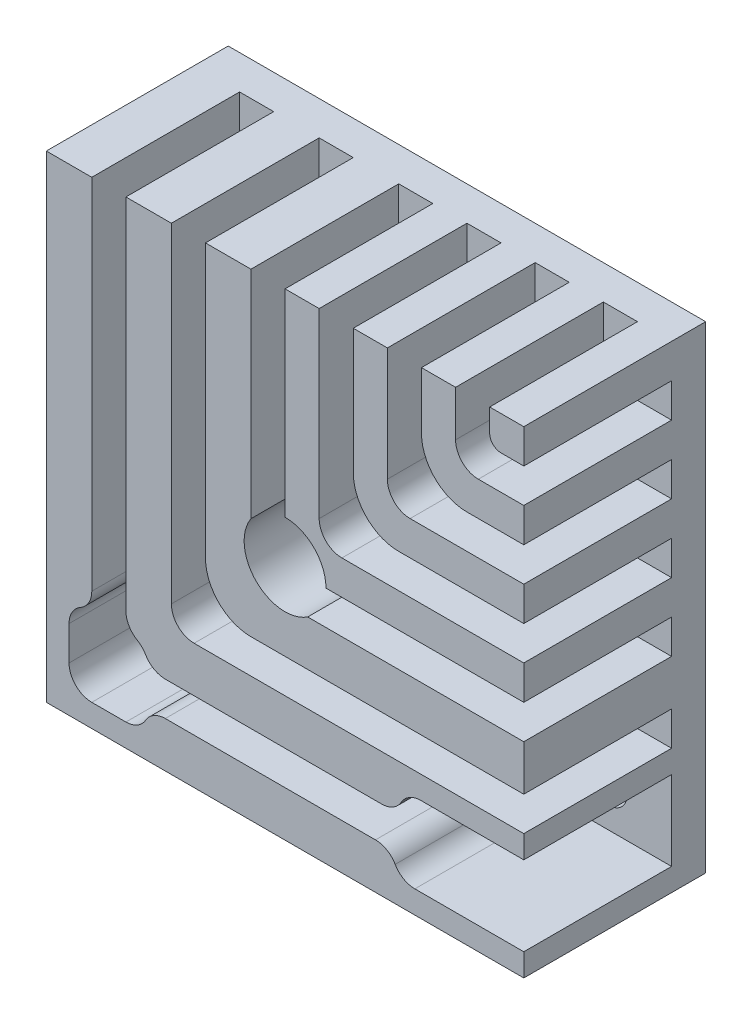
SolidWorks part; units mm, degrees
ref_plane "Front Plane" through (0, 0, 0) normal (0, 0, 1) x (1, 0, 0)
ref_plane "Top Plane" through (0, 0, 0) normal (0, 1, 0) x (1, 0, 0)
ref_plane "Right Plane" through (0, 0, 0) normal (1, 0, 0) x (0, 0, -1)
sketch "Sketch1" plane through (0, 0, 0) normal (0, 0, 1) x (1, 0, 0)
  line L1 (0, 0) -> (42, 0)
  line L2 (0, 0) -> (0, 42)
  line L3 (0, 42) -> (42, 42)
  line L4 (42, 0) -> (42, 42)
  dimension "D1" = 42
  dimension "D2" = 42
extrude "Boss-Extrude1" add sketch "Sketch1" along normal blind 16
sketch "Sketch2" plane through (0, 0, 16) normal (0, 0, 1) x (1, 0, 0)
  line L0 (42, 42) -> (0, 42) construction
  line L1 (42, 0) -> (42, 42) construction
  line L2 (0, 42) -> (0, 0) construction
  line L3 (0, 0) -> (42, 0) construction
  line L4 (38.7689, 42) -> (36.0649, 42)
  line L5 (42, 36.0649) -> (42, 38.7689)
  line L6 (42, 33.5265) -> (42, 30.3811)
  line L7 (33.5265, 42) -> (30.3811, 42)
  line L8 (27.5668, 42) -> (24.7524, 42)
  line L9 (42, 27.5668) -> (42, 24.7524)
  line L10 (42, 21.607) -> (42, 18.572)
  line L11 (42, 15.0403) -> (42, 11.7293)
  line L12 (42, 9.3012) -> (42, 5.6592)
  line L13 (42, 1.079) -> (42, 0)
  line L14 (42, 0) -> (34.9613, 0)
  line L15 (21.607, 42) -> (18.572, 42)
  line L16 (15.0403, 42) -> (11.7293, 42)
  line L17 (9.3012, 42) -> (5.6592, 42)
  line L18 (1.079, 42) -> (0, 42)
  line L19 (0, 42) -> (0, 34.9613)
  line L20 (0, 27.58) -> (0, 15.9232)
  line L21 (0, 9.7979) -> (0, 4.5769)
  line L22 (4.5769, 0) -> (9.7979, 0)
  line L23 (27.58, 0) -> (15.9232, 0)
  arc A0 (38.7689, 42) -> (42, 38.7689) centre (42, 42) ccw
  arc A1 (36.0649, 42) -> (42, 36.0649) centre (42, 42) ccw
  arc A2 (33.5265, 42) -> (42, 33.5265) centre (42, 42) ccw
  arc A3 (30.3811, 42) -> (42, 30.3811) centre (42, 42) ccw
  arc A4 (27.5668, 42) -> (42, 27.5668) centre (42, 42) ccw
  arc A5 (24.7524, 42) -> (42, 24.7524) centre (42, 42) ccw
  arc A6 (21.607, 42) -> (42, 21.607) centre (42, 42) ccw
  arc A7 (18.572, 42) -> (42, 18.572) centre (42, 42) ccw
  arc A8 (15.0403, 42) -> (42, 15.0403) centre (42, 42) ccw
  arc A9 (11.7293, 42) -> (42, 11.7293) centre (42, 42) ccw
  arc A10 (9.3012, 42) -> (42, 9.3012) centre (42, 42) ccw
  arc A11 (5.6592, 42) -> (42, 5.6592) centre (42, 42) ccw
  arc A12 (1.079, 42) -> (42, 1.079) centre (42, 42) ccw
  arc A13 (0, 34.9613) -> (34.9613, 0) centre (42, 42) ccw
  arc A14 (0, 27.58) -> (27.58, 0) centre (42, 42) ccw
  arc A15 (0, 15.9232) -> (15.9232, 0) centre (42, 42) ccw
  arc A16 (0, 9.7979) -> (9.7979, 0) centre (42, 42) ccw
  arc A17 (0, 4.5769) -> (4.5769, 0) centre (42, 42) ccw
extrude "Cut-Extrude1" [suppressed] cut sketch "Sketch2" against normal blind 13
sketch "Sketch3" plane through (0, 0, 16) normal (0, 0, 1) x (1, 0, 0)
  line L2 (39, 42) -> (39, 39)
  line L3 (42, 42) -> (0, 42) construction
  line L4 (39, 39) -> (42, 39)
  line L5 (42, 0) -> (42, 42) construction
  line L6 (42, 36) -> (36, 36)
  line L7 (36, 36) -> (36, 42)
  line L8 (33, 42) -> (33, 33)
  line L9 (33, 33) -> (42, 33)
  line L10 (30, 42) -> (30, 30)
  line L11 (30, 30) -> (42, 30)
  line L12 (42, 27) -> (27, 27)
  line L13 (27, 27) -> (27, 42)
  line L14 (24, 42) -> (24, 24)
  line L15 (24, 24) -> (42, 24)
  line L16 (42, 21) -> (21, 21)
  line L17 (21, 21) -> (21, 42)
  line L18 (18, 42) -> (18, 18)
  line L19 (18, 18) -> (42, 18)
  line L20 (42, 14) -> (14, 14)
  line L21 (14, 14) -> (14, 42)
  line L22 (11, 42) -> (11, 11)
  line L23 (11, 11) -> (42, 11)
  line L24 (42, 7) -> (7, 7)
  line L25 (7, 7) -> (7, 42)
  line L26 (4, 42) -> (4, 4)
  line L27 (4, 4) -> (42, 4)
  line L28 (42, 39) -> (42, 36)
  line L29 (39, 42) -> (36, 42)
  line L30 (33, 42) -> (30, 42)
  line L31 (27, 42) -> (24, 42)
  line L32 (21, 42) -> (18, 42)
  line L33 (14, 42) -> (11, 42)
  line L34 (7, 42) -> (4, 42)
  line L35 (42, 4) -> (42, 7)
  line L36 (42, 11) -> (42, 14)
  line L37 (42, 18) -> (42, 21)
  line L38 (42, 24) -> (42, 27)
  line L39 (42, 30) -> (42, 33)
  dimension "D1" = 3
  dimension "D2" = 3
  dimension "D3" = 3
  dimension "D4" = 3
  dimension "D5" = 3
  dimension "D6" = 3
  dimension "D7" = 3
  dimension "D8" = 3
  dimension "D9" = 4
  dimension "D10" = 3
  dimension "D11" = 4
  dimension "D12" = 3
  dimension "D13" = 3
  dimension "D14" = 3
  dimension "D15" = 3
  dimension "D16" = 3
  dimension "D17" = 3
  dimension "D18" = 3
  dimension "D19" = 3
  dimension "D20" = 3
  dimension "D21" = 4
  dimension "D22" = 3
  dimension "D23" = 4
  dimension "D24" = 3
extrude "Cut-Extrude2" cut sketch "Sketch3" against normal blind 13
fillet "Fillet2" radius 1 1 edges at (39, 39, 9.5) type face fillet first side face at (39, 40.5, 9.5) second side face at (40.5, 39, 9.5)
fillet "Fillet3" radius 4 1 edges at (33, 33, 9.5) type face fillet first side face at (33, 37.5, 9.5) second side face at (37.5, 33, 9.5)
fillet "Fillet4" radius 4 1 edges at (27, 27, 9.5) type face fillet first side face at (27, 34.5, 9.5) second side face at (34.5, 27, 9.5)
fillet "Fillet6" radius 4 1 edges at (14, 14, 9.5) type face fillet first side face at (14, 28, 9.5) second side face at (28, 14, 9.5)
fillet "Fillet8" radius 2 1 edges at (36, 36, 9.5) type face fillet first side face at (36, 39, 9.5) second side face at (39, 36, 9.5)
fillet "Fillet9" radius 2 1 edges at (30, 30, 9.5) type face fillet first side face at (30, 36, 9.5) second side face at (36, 30, 9.5)
fillet "Fillet11" radius 2 1 edges at (18, 18, 9.5) type face fillet first side face at (18, 30, 9.5) second side face at (30, 18, 9.5)
fillet "Fillet12" radius 2 1 edges at (11, 11, 9.5) type face fillet first side face at (11, 26.5, 9.5) second side face at (26.5, 11, 9.5)
fillet "Fillet13" radius 2 1 edges at (4, 4, 9.5) type face fillet first side face at (4, 23, 9.5) second side face at (23, 4, 9.5)
sketch "Sketch4" plane through (0, 0, 0) normal (0, 0, -1) x (-1, 0, 0)
  line L0 (-42, 5.5) -> (0, 5.5) construction
  line L1 (-42, 0) -> (-42, 42) construction
  line L2 (0, 42) -> (0, 0) construction
  line L3 (-5.5, 0) -> (-5.5, 42) construction
  line L4 (0, 0) -> (-42, 0) construction
  line L5 (-42, 42) -> (0, 42) construction
  line L6 (-36.5, 0) -> (-36.5, 42) construction
  line L7 (-21, 0) -> (-21, 42) construction
  line L8 (-42, 21) -> (0, 21) construction
  circle A0 centre (-36.5, 5.5) radius 1.6
  circle A1 centre (-5.5, 5.5) radius 1.6
  circle A2 centre (-21, 21) radius 3.6
  dimension "D4" = 3.2
  dimension "D5" = 7.2
  dimension "D1" = 5.5
  dimension "D2" = 5.5
  dimension "D3" = 5.5
extrude "Cut-Extrude3" cut sketch "Sketch4" against normal up to next
sketch "Sketch5" plane through (0, 0, 16) normal (0, 0, 1) x (1, 0, 0)
  line L16 (30.9533, 9) -> (42.0467, 2) construction
  line L17 (30.9533, 2) -> (42.0467, 2)
  line L18 (30.9533, 2) -> (30.9533, 9)
  line L19 (30.9533, 9) -> (42.0467, 9)
  line L20 (42.0467, 2) -> (42.0467, 9)
  line L21 (42.0467, 9) -> (30.9533, 2) construction
  line L22 (5.5, 9) -> (5.5, 2) construction
  line L23 (2, 2) -> (9, 2)
  line L24 (2, 2) -> (2, 9)
  line L25 (2, 9) -> (9, 9)
  line L26 (9, 2) -> (9, 9)
  line L27 (2, 5.5) -> (9, 5.5) construction
  arc A10 (37.0568, 4) -> (37.0568, 7) centre (36.5, 5.5) ccw construction
  arc A11 (6.0568, 4) -> (4, 6.0568) centre (5.5, 5.5) ccw construction
  point P4 (36.5, 5.5)
  point P18 (5.5, 5.5)
  dimension "D1" = 7
  dimension "D2" = 7
  dimension "D3" = 7
extrude "Cut-Extrude14" cut sketch "Sketch5" against normal blind 13
fillet "Fillet14" radius 2 1 edges at (24, 24, 9.5) type face fillet first side face at (24, 33, 9.5) second side face at (33, 24, 9.5)
fillet "Fillet15" radius 2 1 edges at (9, 2, 9.5) type face fillet first side face at (9, 3, 9.5) second side face at (5.5, 2, 9.5)
fillet "Fillet16" radius 2 1 edges at (2, 2, 9.5) type face fillet first side face at (2, 5.5, 9.5) second side face at (4.5, 2, 9.5)
fillet "Fillet17" radius 2 1 edges at (2, 9, 9.5) type face fillet first side face at (2, 6.5, 9.5) second side face at (3, 9, 9.5)
fillet "Fillet18" radius 2 1 edges at (9, 9, 9.5) type face fillet first side face at (8, 9, 9.5) second side face at (9, 8, 9.5)
fillet "Fillet19" radius 2 1 edges at (4, 9, 9.5) type face fillet first side face at (4, 25.5, 9.5) second side face at (2.7929, 8.2071, 9.5)
fillet "Fillet20" radius 2 1 edges at (7, 9, 9.5) type face fillet first side face at (7, 25.5, 9.5) second side face at (8.2071, 8.2071, 9.5)
fillet "Fillet21" radius 2 1 edges at (9, 7, 9.5) type face fillet first side face at (8.616, 7.933, 9.5) second side face at (19.9766, 7, 9.5)
fillet "Fillet22" radius 2 1 edges at (9, 4, 9.5) type face fillet first side face at (8.2071, 2.7929, 9.5) second side face at (19.9766, 4, 9.5)
fillet "Fillet23" radius 2 1 edges at (30.9533, 9, 9.5) type face fillet first side face at (30.9533, 8, 9.5) first side face at (20.7087, 7, 9.5) second side face at (36.4766, 9, 9.5)
fillet "Fillet24" radius 2 1 edges at (30.9533, 7, 9.5) type face fillet first side face at (31.7462, 8.2071, 9.5) second side face at (20.7087, 7, 9.5)
fillet "Fillet25" radius 2 1 edges at (30.9533, 4, 9.5) type face fillet first side face at (30.9533, 3, 9.5) second side face at (20.7087, 4, 9.5)
fillet "Fillet26" radius 2 1 edges at (30.9533, 2, 9.5) type face fillet first side face at (30.1604, 3.2071, 9.5) first side face at (19.7087, 4, 9.5) second side face at (36.4766, 2, 9.5)
